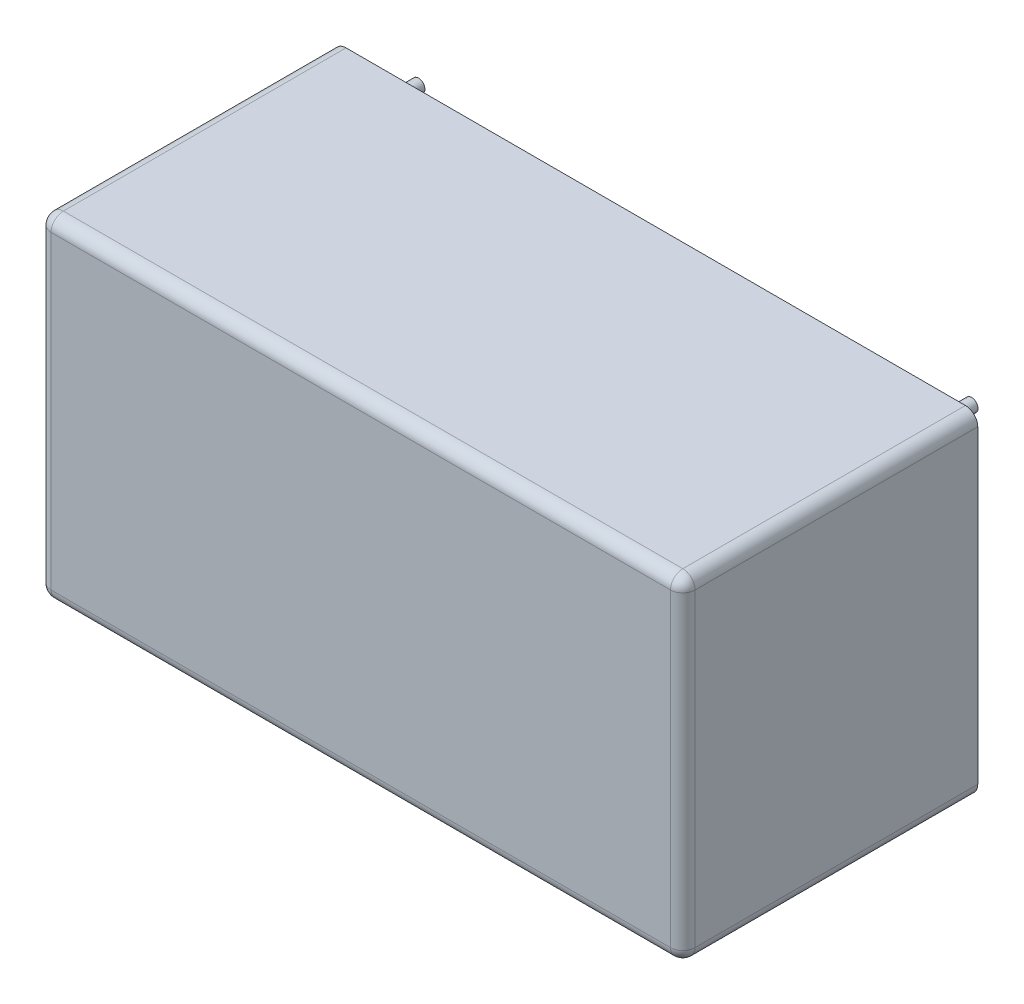
SolidWorks part; units mm, degrees
ref_plane "Plan de face" through (0, 0, 0) normal (0, 0, 1) x (1, 0, 0)
ref_plane "Plan de dessus" through (0, 0, 0) normal (0, 1, 0) x (1, 0, 0)
ref_plane "Plan de droite" through (0, 0, 0) normal (1, 0, 0) x (0, 0, -1)
sketch "Esquisse1" plane through (0, 0, 0) normal (0, 0, 1) x (1, 0, 0)
  line L0 (0, 13.6) -> (0, 0) construction
  line L1 (-25.2, 13.6) -> (25.2, 13.6)
  line L2 (-26.2, 12.6) -> (-26.2, -12.6)
  line L3 (-25.2, -13.6) -> (25.2, -13.6)
  line L4 (26.2, 12.6) -> (26.2, -12.6)
  line L5 (0, 0) -> (26.2, 0) construction
  circle A0 centre (-22.8, 10.4) radius 0.52
  circle A1 centre (-22.8, -10.4) radius 0.52
  circle A2 centre (22.2, 10.4) radius 0.52
  circle A3 centre (22.2, 2.4) radius 0.52
  arc A4 (25.2, 13.6) -> (26.2, 12.6) centre (25.2, 12.6) cw
  arc A5 (-26.2, -12.6) -> (-25.2, -13.6) centre (-25.2, -12.6) ccw
  arc A6 (-25.2, 13.6) -> (-26.2, 12.6) centre (-25.2, 12.6) ccw
  arc A7 (25.2, -13.6) -> (26.2, -12.6) centre (25.2, -12.6) ccw
  point P0 (0, 0)
  dimension "D3" = 1.04
  dimension "D6" = 1.04
  dimension "D8" = 20.8
  dimension "D9" = 1.04
  dimension "D10" = 1.04
  dimension "D11" = 8
  dimension "D13" = 45
  dimension "D14" = 1
  dimension "D4" = 3.2
  dimension "D5" = 3.4
  dimension "D7" = 3.4
  dimension "D12" = 3.2
extrude "Boss.-Extru.1" add sketch "Esquisse1" along normal blind 24 contours L1 A4 L4 A7 L3 A5 L2 A6
fillet "Congé1" radius 1 8 edges at (0, 13.6, 24) (25.9071, 13.3071, 24) (26.2, 0, 24) (25.9071, -13.3071, 24) (0, -13.6, 24) (-25.9071, -13.3071, 24) (-26.2, 0, 24) (-25.9071, 13.3071, 24)
extrude "Boss.-Extru.2" add sketch "Esquisse1<3>" against normal blind 3.5 contours A2 | A3 | A0 | A1
sketch "Esquisse1<3>" plane through (0, 0, 0) normal (0, 0, 1) x (1, 0, 0) same geometry as "Esquisse1"
